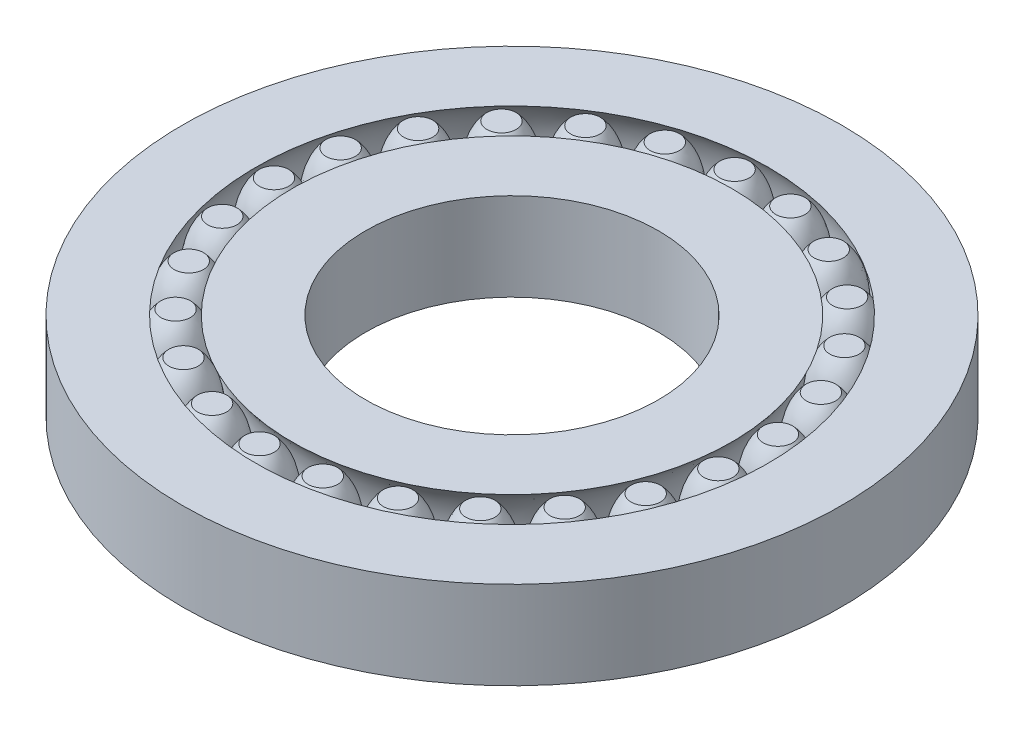
SolidWorks part; units mm, degrees
ref_plane "Front Plane" through (0, 0, 0) normal (0, 0, 1) x (1, 0, 0)
ref_plane "Top Plane" through (0, 0, 0) normal (0, 1, 0) x (1, 0, 0)
ref_plane "Right Plane" through (0, 0, 0) normal (1, 0, 0) x (0, 0, -1)
sketch "Sketch1" plane through (0, 0, 0) normal (0, 0, 1) x (1, 0, 0)
  line L1 (-10, 3) -> (-15, 3)
  line L4 (-16.25, 0) -> (-10, 0) construction
  line L7 (-16.25, 0) -> (-16.25, 3) construction
  line L13 (0, 0) -> (0, 4.657) construction
  line L14 (-10, 3) -> (-10, -3)
  line L15 (-16.25, 3) -> (-15.25, 3) construction
  line L16 (-10, -3) -> (-15, -3)
  line L17 (-22.5, -3) -> (-17.5, -3)
  line L18 (-22.5, 3) -> (-22.5, -3)
  line L19 (-22.5, 3) -> (-17.5, 3)
  ellipse E0 centre (-16.25, 0) end of major axis (-16.25, 3.4641) minor radius 2 (-14.25, 0) -> (-15.25, 3) ccw construction
  ellipse E1 centre (-16.25, 0) end of major axis (-16.25, 3.608) minor radius 2.25 (-15, 3) -> (-15, -3) cw
  ellipse E2 centre (-16.25, 0) end of major axis (-16.25, 3.608) minor radius 2.25 (-17.5, 3) -> (-17.5, -3) ccw
  point P2 (-14.951, 3.0175)
  point P6 (-13.9242, 0)
  point P12 (0, 0)
  point P14 (-16.3018, 0)
  point P31 (-14, 0)
  dimension "D4" = 1
  dimension "D1" = 10
  dimension "D2" = 5
  dimension "D3" = 3
  dimension "D5" = 0.25
  dimension "D6" = 2
  dimension "D7" = 0.25
  dimension "D8" = 3.4641
revolve "Revolve1" add sketch "Sketch1" angle 360 about L13
sketch "Sketch3" plane through (0, 0, 0) normal (0, 0, 1) x (1, 0, 0)
  line L0 (17.5, 3) -> (-17.5, 3) construction
  line L1 (-15.25, 3) -> (-16.25, 3)
  line L2 (-16.25, 3) -> (-16.25, 0) construction
  line L3 (-16.25, 0) -> (-14.25, 0) construction
  line L4 (-15.25, -3) -> (-16.25, -3)
  line L5 (-16.25, -3) -> (-16.25, 3)
  ellipse E0 centre (-16.25, 0) end of major axis (-16.25, 3.4641) minor radius 2 (-15.25, 3) -> (-15.25, -3) cw
  dimension "D1" = 16.25
  dimension "D2" = 2
  dimension "D4" = 15.25
revolve "Revolve2" add sketch "Sketch3" angle 360 about L5
ref_axis "Axis1" through (0, 3, 0) along (0, -1, 0)
pattern_circular "CirPattern7" count 25 over 360 about axis through (0, 3, 0) along (0, -1, 0) of bodies 105
